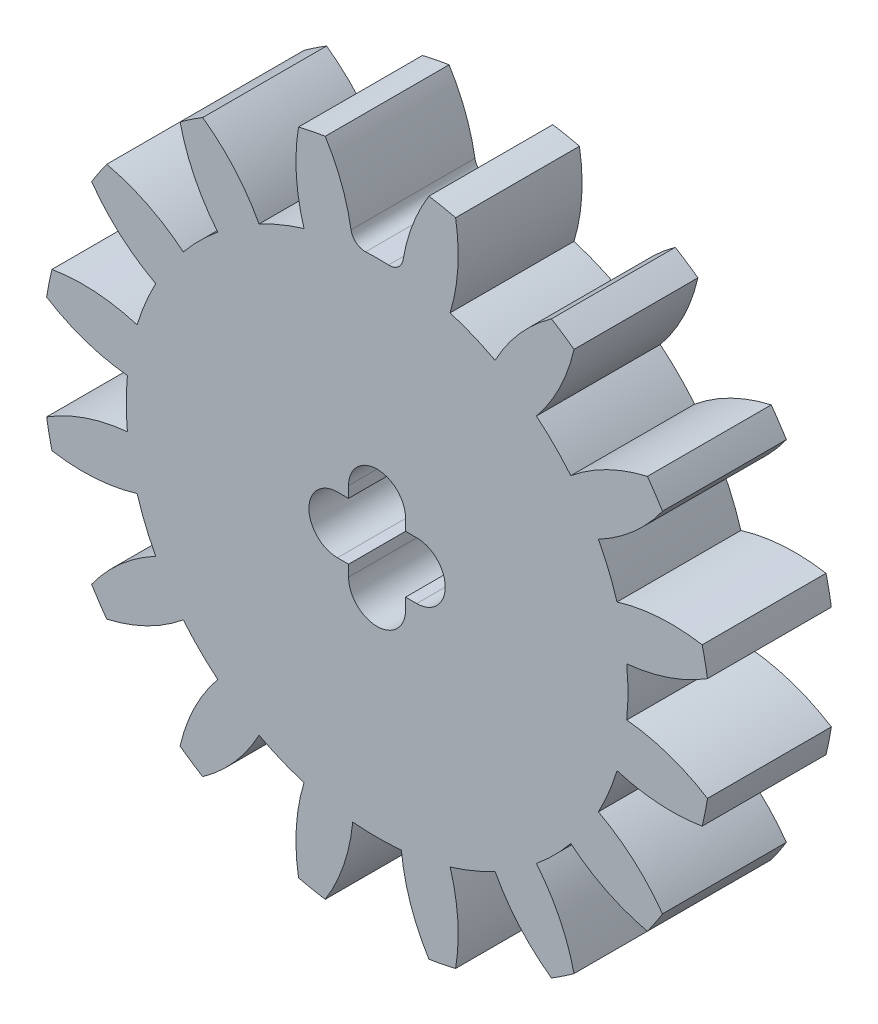
SolidWorks part; units mm, degrees
ref_plane "Front Plane" through (0, 0, 0) normal (0, 0, 1) x (1, 0, 0)
ref_plane "Top Plane" through (0, 0, 0) normal (0, 1, 0) x (1, 0, 0)
ref_plane "Right Plane" through (0, 0, 0) normal (1, 0, 0) x (0, 0, -1)
sketch "Sketch1" plane through (0, 0, 0) normal (0, 0, 1) x (1, 0, 0)
  line L0 (0, -1.6) -> (0, 1.6) construction
  line L1 (-1.15, -1.6) -> (-1.15, 1.6)
  line L2 (1.15, -1.6) -> (1.15, 1.6)
  line L3 (-1.6, 0) -> (1.6, 0) construction
  line L4 (-1.6, 1.15) -> (1.6, 1.15)
  line L5 (-1.6, -1.15) -> (1.6, -1.15)
  circle A0 centre (0, 0) radius 13.5
  arc A2 (-1.15, -1.6) -> (1.15, -1.6) centre (0, -1.6) ccw
  arc A3 (1.15, 1.6) -> (-1.15, 1.6) centre (0, 1.6) ccw
  arc A4 (-1.6, 1.15) -> (-1.6, -1.15) centre (-1.6, 0) ccw
  arc A5 (1.6, -1.15) -> (1.6, 1.15) centre (1.6, 0) ccw
  point P5 (0, 0)
  point P11 (0, 0)
  dimension "D2" = 27
  dimension "D1" = 5.5
  dimension "D3" = 5.5
  dimension "D4" = 2.3
  dimension "D5" = 2.3
extrude "Boss-Extrude1" add sketch "Sketch1" along normal mid plane 5 contours A0 A5 L5 L2 A2 L1 A4 L4 A3 region at (-13.1182, 0, 0)
sketch "Sketch2" plane through (0, 0, 0) normal (0, 0, 1) x (1, 0, 0)
  line L0 (0, 0) -> (0, 13.5) construction
  line L1 (0, 0) -> (-0.9822, 10.0772) construction
  line L2 (0, 8.0719) -> (-4.2467, 19.7397) construction
  arc A0 (1.3999, 11.9181) -> (-1.3999, 11.9181) centre (0, 0) ccw construction
  arc A1 (0.9822, 10.0772) -> (-0.9822, 10.0772) centre (0, 0) ccw
  arc A3 (2.0928, 13.3368) -> (-2.0928, 13.3368) centre (0, 0) ccw
  arc A4 (-0.9822, 10.0772) -> (-2.0928, 13.3368) centre (-8.4601, 9.3484) ccw
  arc A5 (0.9822, 10.0772) -> (2.0928, 13.3368) centre (8.4601, 9.3484) cw
  circle A6 centre (0, 0) radius 13.5 construction
  dimension "D1" = 24
  dimension "D2" = 3.375
  dimension "D3" = 20
  dimension "D4" = 2.8062
extrude "Cut-Extrude1" cut sketch "Sketch2" against normal through all both and the other way through all
fillet "Fillet1" radius 0.57 2 edges at (0.9822, 10.0772, 0) (-0.9822, 10.0772, 0)
pattern_circular "CirPattern3" count 16 over 360 about axis through (0, 0, 2.5) along (0, 0, -1) of "Cut-Extrude1"
equation "\"Module\"= 1.5"
equation "\"Pressure Angle\"= 20"
equation "\"Bore\"= 2"
equation "\"NumTeeth\"= 16"
equation "\"D2@Sketch1\"=(\"NumTeeth\"+2)*\"Module\""
equation "\"D1@Sketch2\"=\"NumTeeth\"*\"Module\""
equation "\"ToothDepth\"= IIF ( \"Module\" < 1.25 , 2.4 * \"Module\" , 2.25 * \"Module\" )"
equation "\"D2@Sketch2\"=\"ToothDepth\""
equation "\"D3@Sketch2\"=\"Pressure Angle\""
equation "\"D4@Sketch2\"=((\"Module\"*PI)/2)+0.3*\"Module\""
equation "\"D1@Fillet1\"=\"Module\"*0.38"
equation "\"D1@CirPattern3\"=\"NumTeeth\""
equation "\"D3@Sketch1\"=\"D1@Sketch1\""
equation "\"D5@Sketch1\"=\"D4@Sketch1\""
